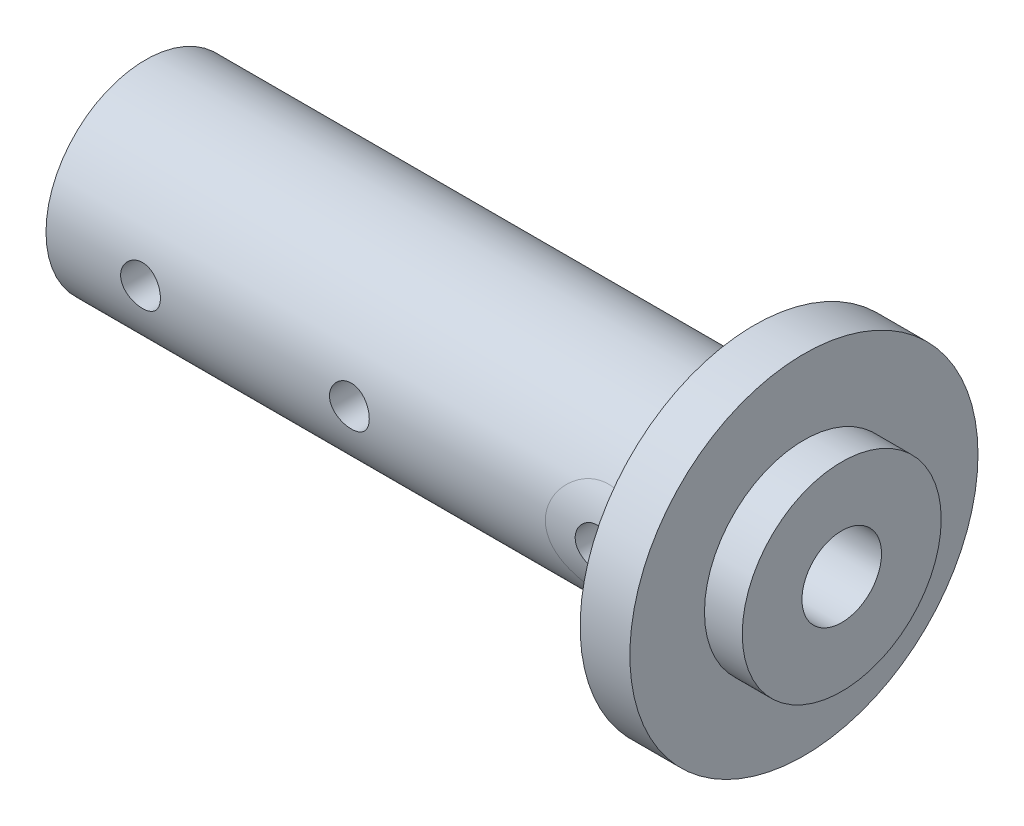
SolidWorks part; units mm, degrees
material "1.0117 (S235J2G4)"
ref_plane "Front Plane" through (0, 0, 0) normal (0, 0, 1) x (1, 0, 0)
ref_plane "Top Plane" through (0, 0, 0) normal (0, 1, 0) x (1, 0, 0)
ref_plane "Right Plane" through (0, 0, 0) normal (1, 0, 0) x (0, 0, -1)
sketch "Sketch1" plane through (0, 0, 0) normal (0, 1, 0) x (1, 0, 0)
  line L1 (-3.8, 17.5) -> (-8.8, 17.5)
  line L2 (-8.8, 17.5) -> (-8.8, 10)
  line L3 (-8.8, 10) -> (-70, 10)
  line L4 (-70, 10) -> (-70, 0)
  line L5 (-70, 0) -> (0, 0) construction
  line L6 (0, 0) -> (-70, 0)
  line L7 (-3.8, 17.5) -> (-3.8, 10)
  line L8 (-3.8, 10) -> (0, 10)
  line L9 (0, 10) -> (0, 4)
  line L10 (0, 4) -> (-70, 4)
  line L11 (-70, 4) -> (-70, 0)
  dimension "D1" = 5
  dimension "D2" = 17.5
  dimension "D3" = 10
  dimension "D4" = 70
  dimension "D5" = 3.8
  dimension "D6" = 4
  dimension "D7" = 70
revolve "Revolve2" add sketch "Sketch1" angle 360 about L6 region at (-32.6475, 0, -7.5533)
sketch "Sketch5" plane through (0, 0, 0) normal (0, 0, 1) x (1, 0, 0)
  line L0 (-8.8, 17.5) -> (-8.8, -17.5) construction
  circle A0 centre (-39.5, 0) radius 2
  circle A1 centre (-60.5, 0) radius 2
  circle A2 centre (-39.5, 0) radius 2 construction
  circle A3 centre (-60.5, 0) radius 2 construction
  circle A4 centre (-14.8, 0) radius 2
  dimension "D1" = 6
extrude "Cut-Extrude2" cut sketch "Sketch5" against normal through all both and the other way through all
sketch "Sketch6" plane through (0, 0, 0) normal (0, 0, 1) x (1, 0, 0)
  circle A0 centre (-14.8, 0) radius 5
  dimension "D1" = 10
split line "Split Line1"
